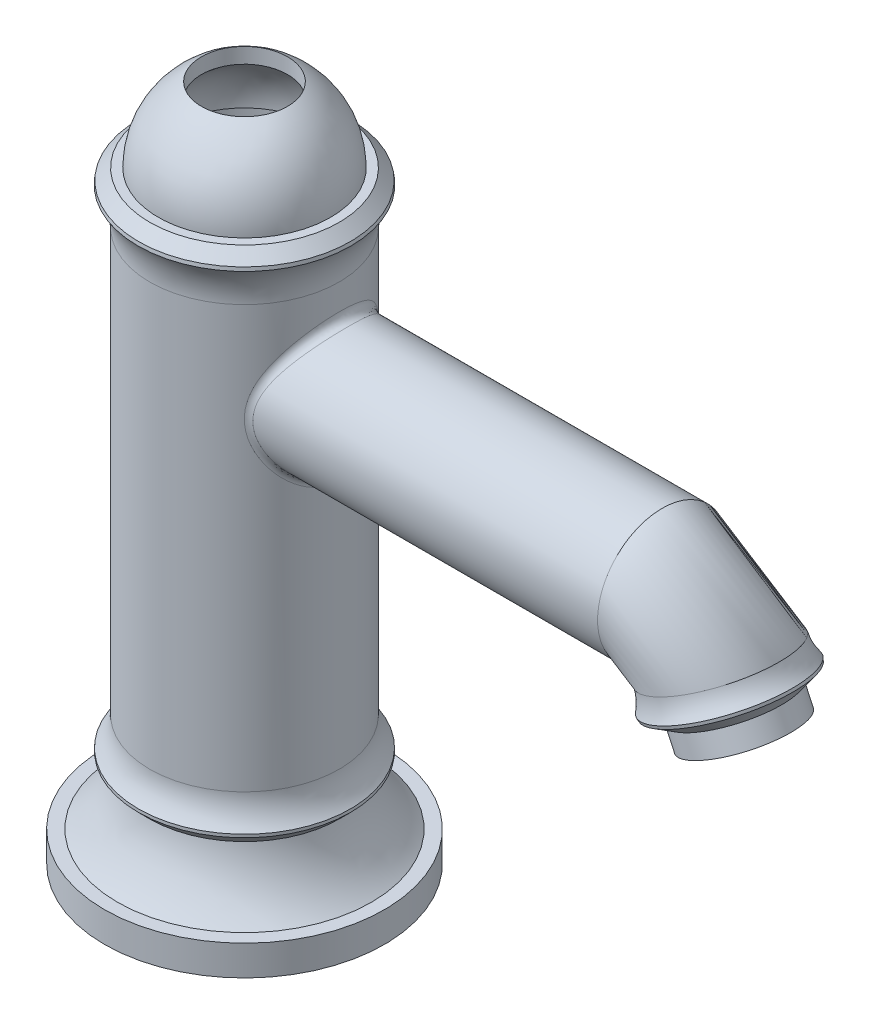
SolidWorks part; units mm, degrees
note: The reader was unsure of these and kept them because the rebuilt part matched: shared geometry of "Sketch3<3>".
material "Nickel"
ref_plane "Front Plane" through (0, 0, 0) normal (0, 0, 1) x (1, 0, 0)
ref_plane "Top Plane" through (0, 0, 0) normal (0, 1, 0) x (1, 0, 0)
ref_plane "Right Plane" through (0, 0, 0) normal (1, 0, 0) x (0, 0, -1)
sketch "Sketch1" plane through (0, 0, 0) normal (0, 0, 1) x (1, 0, 0)
  line L0 (211.6658, 371.6325) -> (327.6658, 371.6325) construction
  line L1 (0, 0) -> (32.5, 0)
  line L2 (32.5, 0) -> (32.5, 7)
  line L3 (32.5, 7) -> (29.5, 7)
  line L4 (22, 128) -> (22, 30)
  line L5 (0, 140) -> (22, 140)
  line L6 (22, 140) -> (25, 137)
  line L7 (25, 23) -> (22, 20)
  line L8 (0, 0) -> (0, 140) construction
  line L9 (0, 140) -> (0, 0)
  arc A0 (25, 137) -> (22, 128) centre (37, 128) ccw
  arc A1 (22, 30) -> (25, 23) centre (31.6667, 30) ccw
  arc A2 (22, 20) -> (29.5, 7) centre (43.6632, 23.8346) ccw
  dimension "D2" = 140
  dimension "D12" = 22
  dimension "D15" = 15
  dimension "D1" = 116
  dimension "D3" = 45
  dimension "D4" = 7
  dimension "D5" = 3
  dimension "D6" = 45
  dimension "D7" = 20
  dimension "D8" = 30
  dimension "D9" = 32.5
  dimension "D10" = 25
  dimension "D11" = 22
  dimension "D14" = 3
revolve "Revolve1" add sketch "Sketch1" angle 360 about L9
sketch "Sketch2" plane through (0, 0, 0) normal (0, 0, 1) x (1, 0, 0)
  line L0 (0.5027, 43.0333) -> (116.5027, 43.0333) construction
  dimension "D1" = 116
sketch "Sketch3" plane through (0, 0, 0) normal (0, 0, 1) x (1, 0, 0)
  line L0 (0, 105) -> (97, 105)
  line L1 (110.5946, 96.3393) -> (116, 84.7474) construction
  line L2 (0, 0) -> (0, 140) construction
  line L3 (22, 140) -> (-22, 140) construction
  line L4 (-32.5, 0) -> (32.5, 0) construction
  arc A0 (97, 105) -> (110.5946, 96.3393) centre (97, 90) cw
  dimension "D1" = 116
  dimension "D3" = 15
  dimension "D2" = 25
  dimension "D4" = 105
  dimension "D5" = 97
sweep "Sweep1" add path "Sketch3" circular profile diameter 30 parameters "D3"=30
sketch "Sketch16" plane through (0, 0, 0) normal (0, 0, 1) x (1, 0, 0)
  line L0 (116, 84.7474) -> (126.8757, 89.8188)
  line L1 (126.8757, 89.8188) -> (124.7626, 94.3504)
  line L2 (124.7626, 94.3504) -> (127.6506, 98.621)
  line L3 (97, 90) -> (124.1892, 102.6785) construction
  line L5 (124.1892, 102.6785) -> (110.5946, 96.3393)
  line L6 (110.5946, 96.3393) -> (116, 84.7474)
  arc A0 (127.6506, 98.621) -> (124.1892, 102.6785) centre (133.2523, 106.9047) cw
  arc A1 (124.1892, 102.6785) -> (97, 120) centre (97, 90) ccw construction
  dimension "D1" = 12
  dimension "D2" = 10
  dimension "D3" = 5
revolve "Revolve3" add sketch "Sketch16" angle 360 about L6
chamfer "Chamfer1" distance 0.5 angle 45 3 edges at (0, 137, 25) (0, 23, 25) (97.8834, 84.7403, 0)
sweep "Cut-Sweep1" cut path "Sketch3<3>" circular profile diameter 20 parameters "D3"=20
sketch "Sketch3<3>" plane through (0, 0, 0) normal (0, 0, 1) x (1, 0, 0) same geometry as "Sketch3"
sketch "Sketch39" plane through (-11.7418, 25.1804, 0) normal (0.4226, -0.9063, 0) x (-0.9063, -0.4226, 0)
  line L0 (-140.9475, 0) -> (-132.2868, 0) construction
  circle A0 centre (-140.9475, 0) radius 10.414
  circle A1 centre (-140.9475, 0) radius 12 construction
  dimension "D1" = 20.828
extrude "Cut-Extrude1" cut sketch "Sketch39" against normal up to vertex (12.7902 mm away) up to point (110.5946, 96.3393, 0)
fillet "Fillet1" radius 2 1 edges at (21.8483, 90.2234, -2.579)
sketch "Sketch65" plane through (0, 0, 0) normal (0, 0, 1) x (1, 0, 0)
  line L0 (22, 140) -> (-22, 140) construction
  line L1 (20, 140) -> (17, 140)
  line L2 (0, 160) -> (0, 140) construction
  line L3 (0, 160) -> (0, 157)
  arc A0 (20, 140) -> (0, 160) centre (0, 140) ccw
  arc A1 (17, 140) -> (0, 157) centre (0, 140) ccw
  circle A2 centre (0, 140) radius 20 construction
  circle A3 centre (0, 140) radius 17 construction
  dimension "D1" = 40
  dimension "D2" = 3
revolve "Revolve4" add sketch "Sketch65" angle 360 about L2
sketch "Sketch66" plane through (0, 0, 0) normal (0, -1, 0) x (1, 0, 0)
  circle A0 centre (0, 0) radius 19
  circle A1 centre (0, 0) radius 22 construction
  circle A2 centre (0, 0) radius 22 construction
  dimension "D1" = 3
extrude "Cut-Extrude3" cut sketch "Sketch66" against normal up to surface (140 mm away) up to face at (0, 140, 22)
sketch "Sketch67" plane through (0, 140, 0) normal (0, 1, 0) x (1, 0, 0)
  circle A0 centre (0, 0) radius 10
  dimension "D1" = 20
extrude "Cut-Extrude4" cut sketch "Sketch67" along normal through all
